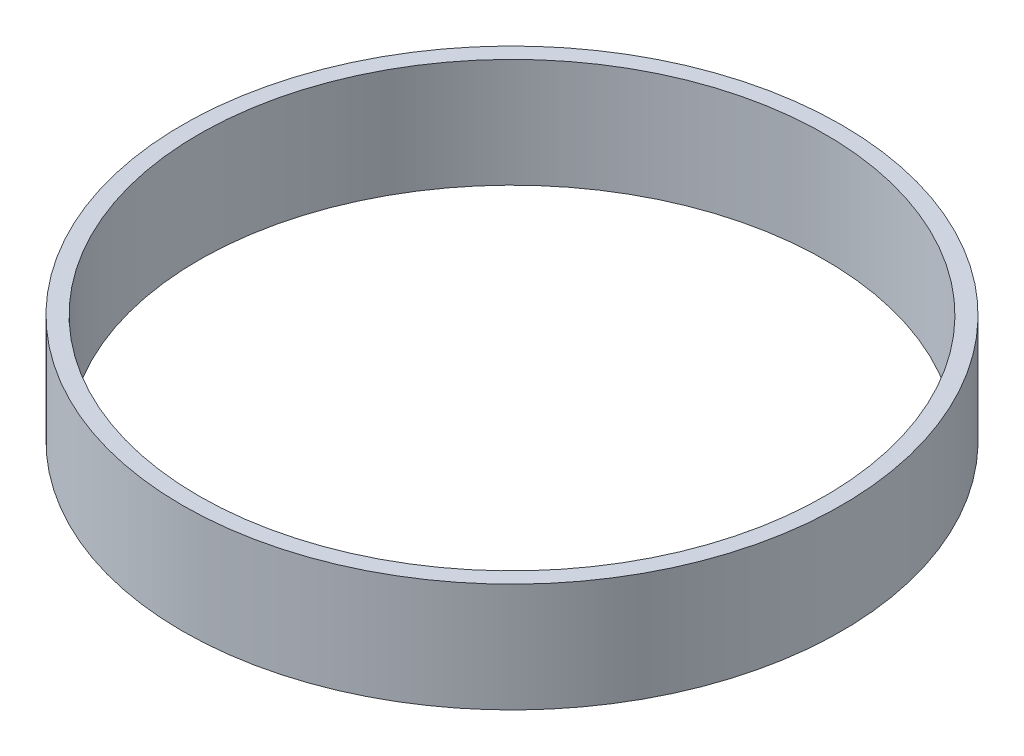
SolidWorks part; units mm, degrees
ref_plane "Front Plane" through (0, 0, 0) normal (0, 0, 1) x (1, 0, 0)
ref_plane "Top Plane" through (0, 0, 0) normal (0, 1, 0) x (1, 0, 0)
ref_plane "Right Plane" through (0, 0, 0) normal (1, 0, 0) x (0, 0, -1)
sketch "Base" plane through (0, 0, 0) normal (0, 1, 0) x (1, 0, 0)
  circle A0 centre (0, 0) radius 115
  circle A1 centre (0, 0) radius 121
  dimension "D1" = 230
  dimension "D2" = 6
extrude "Base-Extrude" add sketch "Base" along normal blind 40
hole_wizard "CSK for M5 Countersunk Raised Head Screw1" positions "Sketch1" profile "Sketch2" countersink size "M5" standard "ISO"
sketch "Sketch1" plane through (37.9687, -4, -14.4349) normal (0, -1, 0) x (-1, 0, 0)
  circle A0 centre (37.9687, -14.4349) radius 118
  point P28 (-80.0313, -14.4349)
  point P38 (-45.4699, 69.0037)
  point P39 (37.9687, 103.5651)
  point P40 (121.4073, 69.0037)
  point P41 (155.9687, -14.4349)
  point P42 (121.4073, -97.8735)
  point P43 (37.9687, -132.4349)
  point P44 (-45.4699, -97.8735)
  point P48 (0, 0)
  point P49 (155.8785, -9.8209)
  point P50 (37.9687, 103.5651)
sketch "Sketch2" plane through (83.4386, -4, 83.4386) normal (1, 0, 0) x (0, 0, -1)
  line L0 (0, 0) -> (0, 21.6524)
  line L1 (0, 21.6524) -> (2.75, 20)
  line L2 (2.75, 20) -> (2.75, 2.45)
  line L3 (2.75, 2.45) -> (5.2, 0)
  line L4 (5.2, 0) -> (0, 0)
  line L5 (-2.75, 2.45) -> (-5.2, 0) construction
  line L6 (0, 21.6524) -> (-2.75, 20) construction
  line L7 (0, -6.35) -> (0, 107.95) construction
  dimension "Hole Dia." = 5.5
  dimension "Hole Depth" = 20
  dimension "Near C'Sink Dia." = 10.4
  dimension "Near C'Sink Angle" = 90
  dimension "Drill Angle" = 118
equation "\"inner radius\"= 230"
equation "\"wall thickness\"= 6\t"
equation "\"outer radius\"= \"inner radius\" + 2 * \"wall thickness\""
equation "\"D2@Base\"=\"wall thickness\""
equation "\"D1@Base\"=\"inner radius\""
equation "\"height\" = 40"
equation "\"D1@Base-Extrude\"=\"height\""
equation "\"wheel distance\" = 100"
